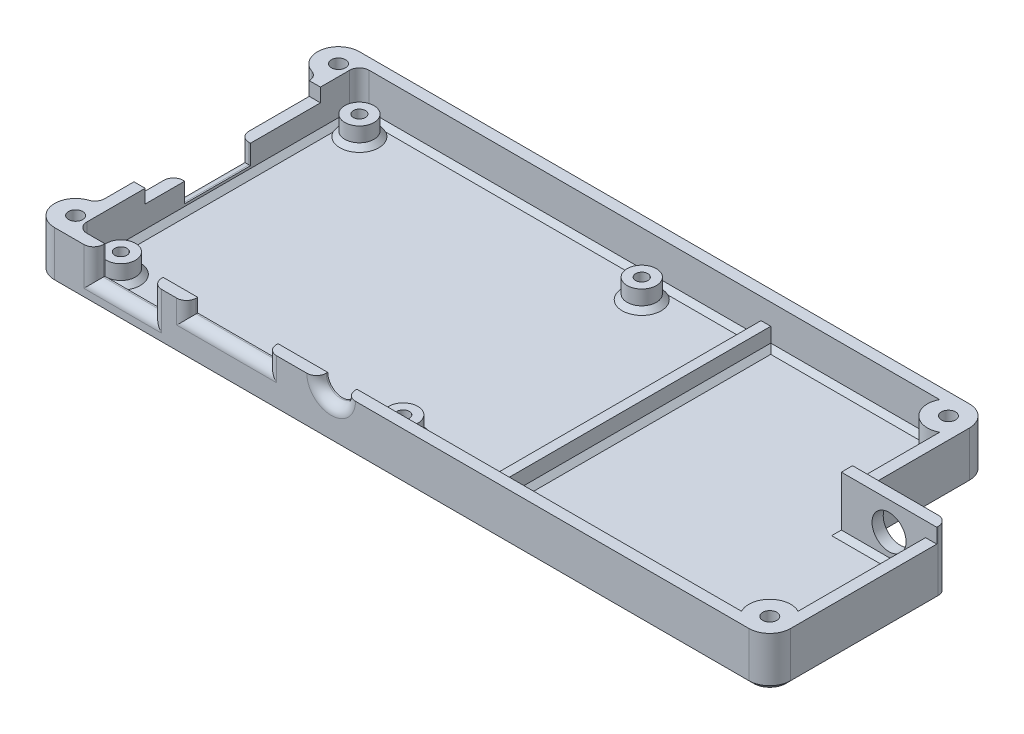
SolidWorks part; units mm, degrees
ref_plane "Front Plane" through (0, 0, 0) normal (0, 0, 1) x (1, 0, 0)
ref_plane "Top Plane" through (0, 0, 0) normal (0, 1, 0) x (1, 0, 0)
ref_plane "Right Plane" through (0, 0, 0) normal (1, 0, 0) x (0, 0, -1)
sketch "Sketch1" plane through (0, 0, 0) normal (0, 1, 0) x (1, 0, 0)
  line L0 (-71.5618, 3.106) -> (51.4382, 3.106) construction
  line L1 (-71.5618, 31.106) -> (51.4382, 31.106)
  line L2 (-71.5618, 31.106) -> (-71.5618, -24.894)
  line L3 (-71.5618, -24.894) -> (51.4382, -24.894)
  line L4 (51.4382, 31.106) -> (51.4382, -24.894)
  line L5 (-60.6618, -24.894) -> (-60.6618, -31.6828) construction
  line L6 (-68.0618, 27.606) -> (-10.0618, 27.606)
  line L7 (-68.0618, 27.606) -> (-68.0618, -21.394)
  line L8 (-68.0618, -21.394) -> (-10.0618, -21.394)
  line L9 (-10.0618, 27.606) -> (-10.0618, -21.394)
  line L10 (-39.5618, -24.894) -> (-39.5618, -31.6828) construction
  line L11 (-18.0618, -24.894) -> (-18.0618, -31.6828) construction
  line L12 (-65.4118, -26.5648) -> (-55.9118, -26.5648) construction
  line L13 (-48.0618, -26.5648) -> (-31.0618, -26.5648) construction
  line L14 (-22.0618, -26.5648) -> (-14.0618, -26.5648) construction
  line L15 (-72.5618, 9.606) -> (-72.5618, -3.394) construction
  line L16 (-71.5618, 3.106) -> (-72.5618, 3.106) construction
  dimension "D1" = 123
  dimension "D2" = 56
  dimension "D3" = 49
  dimension "D4" = 58
  dimension "D5" = 3.5
  dimension "D6" = 3.5
  dimension "D7" = 10.9
  dimension "D8" = 32
  dimension "D9" = 53.5
  dimension "D10" = 2
  dimension "D11" = 13
  dimension "D12" = 9.5
  dimension "D13" = 17
  dimension "D14" = 8
sketch "Sketch3" plane through (0, 0, 0) normal (0, 1, 0) x (1, 0, 0)
  line L0 (57.0382, -25.894) -> (69.7382, -25.894)
  line L1 (54.7382, 8.406) -> (72.0382, 8.406)
  line L2 (57.0382, 6.106) -> (69.7382, 6.106) construction
  line L3 (54.7382, -28.194) -> (72.0382, -28.194)
  line L4 (54.7382, 34.406) -> (-74.8618, 34.406)
  line L5 (-74.8618, 34.406) -> (-74.8618, -28.194)
  line L6 (-74.8618, -28.194) -> (54.7382, -28.194)
  line L7 (54.7382, 8.406) -> (54.7382, 34.406)
  line L8 (52.4382, 32.106) -> (-72.5618, 32.106)
  line L9 (52.4382, -25.894) -> (52.4382, 32.106)
  line L10 (-72.5618, -25.894) -> (52.4382, -25.894)
  line L11 (-72.5618, 32.106) -> (-72.5618, -25.894)
  line L12 (52.4382, 32.106) -> (-72.5618, 32.106)
  line L13 (52.4382, 6.106) -> (52.4382, 32.106)
  line L14 (-72.5618, -25.894) -> (52.4382, -25.894)
  line L15 (-72.5618, 32.106) -> (-72.5618, -25.894)
  line L16 (-10.0618, 3.106) -> (-10.0618, 34.406) construction
  line L17 (-71.5618, 3.106) -> (51.4382, 3.106) construction
  line L18 (72.0382, 8.406) -> (72.0382, -28.194)
  line L19 (69.7382, 6.106) -> (69.7382, -25.894)
  line L20 (-74.8618, 3.106) -> (52.7382, 3.106) construction
  line L21 (52.4382, 6.106) -> (69.7382, 6.106)
  line L22 (57.0382, -25.894) -> (52.4382, -25.894)
  line L23 (57.0382, 6.106) -> (57.0382, -25.894) construction
  line L24 (54.7382, 8.406) -> (54.7382, -28.194) construction
  line L25 (54.7382, -28.194) -> (54.7382, 34.406) construction
  line L26 (52.4382, -25.894) -> (52.4382, 32.106) construction
  dimension "D3" = 2.3
  dimension "D4" = 26
  dimension "D5" = 15
  dimension "D1" = 1
  dimension "D2" = 2.3
extrude "Boss-Extrude1" add sketch "Sketch3" along normal blind 10.3
sketch "Sketch5" plane through (0, 0, 0) normal (0, 1, 0) x (1, 0, 0)
  line L1 (-72.5618, 32.106) -> (52.4382, 32.106)
  line L2 (-72.5618, 32.106) -> (-72.5618, -25.894)
  line L3 (-72.5618, -25.894) -> (50.4382, -25.894)
  line L4 (52.4382, 32.106) -> (52.4382, 6.106)
  line L5 (52.4382, 6.106) -> (69.7382, 6.106)
  line L7 (50.4382, -25.894) -> (69.7382, -25.894)
  line L8 (69.7382, 6.106) -> (69.7382, -25.894)
extrude "Boss-Extrude2" add sketch "Sketch5" along normal blind 2
sketch "Sketch6" plane through (0, 2, 0) normal (0, 1, 0) x (1, 0, 0)
  circle A0 centre (-68.0618, 27.606) radius 3
  circle A1 centre (-68.0618, -21.394) radius 3
  circle A2 centre (-10.0618, -21.394) radius 3
  circle A3 centre (-10.0618, 27.606) radius 3
extrude "Boss-Extrude3" add sketch "Sketch6" along normal blind 4
hole_wizard "Ø2.5 (2.5) Diameter Hole1" positions "Sketch8" profile "Sketch9" hole size "Ø2.5" standard "ANSI Metric"
sketch "Sketch8" plane through (0, 6, 0) normal (0, 1, 0) x (1, 0, 0)
  point P0 (-68.0618, 27.606)
  point P3 (-10.0618, 27.606)
  point P6 (-10.0618, -21.394)
  point P9 (-68.0618, -21.394)
sketch "Sketch9" plane through (-68.0618, 6, -27.606) normal (1, 0, 0) x (0, 0, 1)
  line L0 (0, 0) -> (0, 8.7511)
  line L1 (0, 8.7511) -> (1.25, 8)
  line L2 (1.25, 8) -> (1.25, 0)
  line L5 (1.25, 0) -> (0, 0)
  line L10 (0, 8.7511) -> (-1.25, 8) construction
  line L11 (0, -6.35) -> (0, 107.95) construction
  dimension "Hole Dia." = 2.5
  dimension "Hole Depth" = 8
  dimension "Drill Angle" = 118
sketch "Sketch10" plane through (0, 2, 0) normal (0, 1, 0) x (1, 0, 0)
  line L0 (52.4382, 32.106) -> (-72.5618, 32.106) construction
  line L1 (9.9382, 32.106) -> (11.9382, 32.106)
  line L2 (9.9382, 32.106) -> (9.9382, -25.894)
  line L3 (9.9382, -25.894) -> (11.9382, -25.894)
  line L4 (11.9382, 32.106) -> (11.9382, -25.894)
  line L5 (-72.5618, -25.894) -> (69.7382, -25.894) construction
  line L6 (-10.0618, 27.606) -> (-10.0618, -21.394) construction
  dimension "D1" = 2
  dimension "D2" = 20
extrude "Boss-Extrude4" add sketch "Sketch10" along normal blind 4
sketch "Sketch11" plane through (0, 0, 28.194) normal (0, 0, 1) x (1, 0, 0)
  line L0 (-74.8618, 10.3) -> (-74.8618, 0) construction
  line L1 (-66.8618, 10.3) -> (-54.8618, 10.3)
  line L2 (-66.8618, 10.3) -> (-66.8618, 4.5)
  line L3 (-66.8618, 4.5) -> (-54.8618, 4.5)
  line L4 (-54.8618, 10.3) -> (-54.8618, 4.5)
  line L5 (-74.8618, 0) -> (72.0382, 0) construction
  line L6 (-60.8618, 10.3) -> (-60.6618, 0) construction
  line L7 (-65.4118, 0) -> (-55.9118, 0) construction
  line L9 (-47.778, 10.3) -> (-31.278, 10.3)
  line L10 (-47.778, 10.3) -> (-47.778, 7.5)
  line L11 (-47.778, 7.5) -> (-31.278, 7.5)
  line L12 (-31.278, 10.3) -> (-31.278, 7.5)
  line L13 (-68.0618, 0) -> (-10.0618, 0) construction
  line L14 (-39.5618, 0) -> (-39.528, 10.3) construction
  line L15 (-48.0618, 0) -> (-31.0618, 0) construction
  line L16 (-18.0618, 0) -> (-18.0618, 10.3) construction
  line L17 (-22.0618, 0) -> (-14.0618, 0) construction
  line L18 (-74.8618, 10.3) -> (72.0382, 10.3) construction
  circle A0 centre (-18.0618, 10.3) radius 3
  dimension "D5" = 6
  dimension "D1" = 4.5
  dimension "D2" = 12
  dimension "D3" = 7.5
  dimension "D4" = 16.5
  dimension "D6" = 8
extrude "Cut-Extrude1" cut sketch "Sketch11" against normal up to next
sketch "Sketch12" plane through (-74.8618, 0, 0) normal (-1, 0, 0) x (0, 0, 1)
  line L0 (-3.106, 0) -> (-3.106, 10.3) construction
  line L1 (-27.606, 0) -> (21.394, 0) construction
  line L2 (-34.406, 10.3) -> (28.194, 10.3) construction
  line L4 (-9.7329, 10.3) -> (3.7671, 10.3)
  line L5 (-9.7329, 10.3) -> (-9.7329, 3.5)
  line L6 (-9.7329, 3.5) -> (3.7671, 3.5)
  line L7 (3.7671, 10.3) -> (3.7671, 3.5)
  line L8 (-24.106, 10.3) -> (11.894, 10.3)
  line L9 (-24.106, 10.3) -> (-24.106, 7.5)
  line L10 (-24.106, 7.5) -> (11.894, 7.5)
  line L11 (11.894, 10.3) -> (11.894, 7.5)
  dimension "D1" = 13.5
  dimension "D2" = 3.5
  dimension "D3" = 7.5
  dimension "D4" = 36
extrude "Cut-Extrude2" cut sketch "Sketch12" against normal up to next contours L10 L11 L8 L9 | L7 L6 L5 L4
fillet "Fillet6" radius 2 1 edges at (52.4382, 6.15, -32.106)
fillet "Fillet8" radius 2 2 edges at (-72.5618, 6.15, 25.894) (-72.5618, 6.15, -32.106)
chamfer "Chamfer1" distance 1 angle 45 4 edges at (-68.0618, 2, 24.394) (-10.0618, 2, 24.394) (-10.0618, 2, -24.606) (-68.0618, 2, -24.606)
chamfer "Chamfer2" distance 1 angle 45 13 edges at (11.9382, 2, -3.106) (40.8382, 2, 25.894) (31.1882, 2, -32.106) (51.8524, 2, -31.5202) (52.4382, 2, -18.106) (-30.3118, 2, 25.894) (-71.976, 2, 25.3082) (-72.5618, 2, -3.106) (-71.976, 2, -31.5202) (9.9382, 2, -3.106) (-30.3118, 2, -32.106) (69.7382, 2, 9.894) (61.0882, 2, -6.106)
fillet "Fillet9" radius 2 9 edges at (-74.8618, 5.5, -9.7329) (-74.8618, 3.5, -2.9829) (-74.8618, 5.5, 3.7671) (-18.0618, 7.3, 28.194) (-31.278, 8.9, 28.194) (-47.778, 8.9, 28.194) (-39.528, 7.5, 28.194) (-54.8618, 7.4, 28.194) (-60.8618, 4.5, 28.194)
sketch "Sketch14" plane through (0, 10.3, 0) normal (0, 1, 0) x (1, 0, 0)
  line L1 (52.4382, 6.106) -> (72.0382, 6.106)
  line L2 (52.4382, 6.106) -> (52.4382, 8.406)
  line L3 (52.4382, 8.406) -> (72.0382, 8.406)
  line L4 (72.0382, 6.106) -> (72.0382, 8.406)
extrude "Boss-Extrude5" add sketch "Sketch14" along normal blind 3
sketch "Sketch13" plane through (0, 0, -8.406) normal (0, 0, -1) x (-1, 0, 0)
  circle A0 centre (-62.2382, 7.5443) radius 3.5
extrude "Cut-Extrude3" cut sketch "Sketch13" against normal up to next
sketch "Sketch17" plane through (0, 0, 0) normal (0, 1, 0) x (1, 0, 0)
  line L0 (-74.8618, 34.406) -> (-74.8618, 24.106) construction
  line L1 (-74.8618, 34.406) -> (-74.8618, 25.806)
  line L2 (-74.8618, 25.806) -> (-74.659, 25.9406)
  line L3 (-74.8618, -19.594) -> (-74.8618, -28.194)
  line L4 (-74.8618, -28.194) -> (-74.659, -28.0594)
  arc A0 (-74.8618, -19.594) -> (-74.8618, -28.194) centre (-74.8618, -23.894) ccw
  arc A1 (-74.8618, 34.406) -> (-74.8618, 25.806) centre (-74.8618, 30.106) ccw
extrude "Boss-Extrude6" add sketch "Sketch17" along normal up to vertex (10.3 mm away) contours L1 A1 | L3 A0 region at (-76.6867, 0, -30.106) region at (-76.6867, 0, 23.894) up to point (-74.8618, 10.3, 28.194)
hole_wizard "Ø2.9 (2.9) Diameter Hole2" positions "Sketch19" profile "Sketch18" hole size "Ø2.9" standard "ANSI Metric" end condition up to next
sketch "Sketch19" plane through (0, 10.3, 0) normal (0, 1, 0) x (1, 0, 0)
  point P0 (-74.8618, 30.106)
sketch "Sketch18" plane through (-74.8618, 10.3, -30.106) normal (1, 0, 0) x (0, 0, 1)
  line L0 (0, 0) -> (0, 10.3)
  line L1 (0, 10.3) -> (1.45, 10.3)
  line L2 (1.45, 10.3) -> (1.45, 0)
  line L5 (1.45, 0) -> (0, 0)
  line L11 (0, -6.35) -> (0, 107.95) construction
  dimension "Thru Hole Dia." = 2.9
  dimension "Thru Hole Depth" = 10.3
hole_wizard "Ø2.9 (2.9) Diameter Hole1" positions "Sketch21" profile "Sketch20" hole size "Ø2.9" standard "ANSI Metric" end condition up to next
sketch "Sketch21" plane through (0, 10.3, 0) normal (0, 1, 0) x (1, 0, 0)
  point P0 (-74.8618, -23.894)
sketch "Sketch20" plane through (-74.8618, 10.3, 23.894) normal (1, 0, 0) x (0, 0, 1)
  line L0 (0, 0) -> (0, 10.3)
  line L1 (0, 10.3) -> (1.45, 10.3)
  line L2 (1.45, 10.3) -> (1.45, 0)
  line L5 (1.45, 0) -> (0, 0)
  line L11 (0, -6.35) -> (0, 107.95) construction
  dimension "Thru Hole Dia." = 2.9
  dimension "Thru Hole Depth" = 10.3
sketch "Sketch24" plane through (0, 2, 0) normal (0, 1, 0) x (1, 0, 0)
  line L0 (54.7382, 8.406) -> (54.7382, 34.406) construction
  line L1 (54.7382, 34.406) -> (-74.8618, 34.406) construction
  line L2 (72.0382, -28.194) -> (72.0382, 6.106) construction
  line L5 (-13.0618, -28.194) -> (72.0382, -28.194) construction
  circle A0 centre (67.7382, -23.894) radius 4.3
  circle A1 centre (50.4382, 30.106) radius 4.3
  point P12 (64.455, -28.194)
  dimension "D1" = 4.3
  dimension "D2" = 4.3
  dimension "D3" = 4.3
  dimension "D4" = 4.3
extrude "Boss-Extrude7" add sketch "Sketch24" along normal up to surface (8.3 mm away) up to face at (-74.8618, 10.3, -28.656)
hole_wizard "Ø2.9 (2.9) Diameter Hole3" positions "Sketch26" profile "Sketch25" hole size "Ø2.9" standard "ANSI Metric" end condition up to next
sketch "Sketch26" plane through (0, 10.3, 0) normal (0, 1, 0) x (1, 0, 0)
  point P0 (67.7382, -23.894)
sketch "Sketch25" plane through (67.7382, 10.3, 23.894) normal (1, 0, 0) x (0, 0, 1)
  line L0 (0, 0) -> (0, 10.3)
  line L1 (0, 10.3) -> (1.45, 10.3)
  line L2 (1.45, 10.3) -> (1.45, 0)
  line L5 (1.45, 0) -> (0, 0)
  line L11 (0, -6.35) -> (0, 107.95) construction
  dimension "Thru Hole Dia." = 2.9
  dimension "Thru Hole Depth" = 10.3
hole_wizard "Ø2.9 (2.9) Diameter Hole4" positions "Sketch28" profile "Sketch27" hole size "Ø2.9" standard "ANSI Metric" end condition up to next
sketch "Sketch28" plane through (0, 10.3, 0) normal (0, 1, 0) x (1, 0, 0)
  point P0 (50.4382, 30.106)
sketch "Sketch27" plane through (50.4382, 10.3, -30.106) normal (1, 0, 0) x (0, 0, 1)
  line L0 (0, 0) -> (0, 10.3)
  line L1 (0, 10.3) -> (1.45, 10.3)
  line L2 (1.45, 10.3) -> (1.45, 0)
  line L5 (1.45, 0) -> (0, 0)
  line L11 (0, -6.35) -> (0, 107.95) construction
  dimension "Thru Hole Dia." = 2.9
  dimension "Thru Hole Depth" = 10.3
fillet "Fillet10" radius 4.3 1 edges at (54.7382, 5.15, -34.406)
fillet "Fillet16" radius 4.3 1 edges at (72.0382, 5.15, 28.194)
fillet "Fillet17" radius 2 2 edges at (54.7382, 5.15, -8.406) (72.0382, 6.65, -8.406)
fillet "Fillet18" radius 2 2 edges at (-74.8618, 5.15, 19.594) (-74.8618, 5.15, -25.806)
chamfer "Chamfer3" distance 1 angle 45 14 edges at (53.4788, 0, -33.1466) (-12.2118, 0, -34.406) (54.7382, 0, -20.256) (-79.1058, 0, -30.7975) (55.324, 0, -8.9918) (-75.2385, 0, -25.3002) (63.3882, 0, -8.406) (-74.8618, 0, -3.106) (71.4524, 0, -7.8202) (-75.2385, 0, 19.0883) (72.0382, 0, 8.744) (-79.1058, 0, 24.5855) (70.7788, 0, 26.9346) (-3.5618, 0, 28.194)
fillet "Fillet19" radius 2 1 edges at (-66.8618, 6.4, 28.194)
